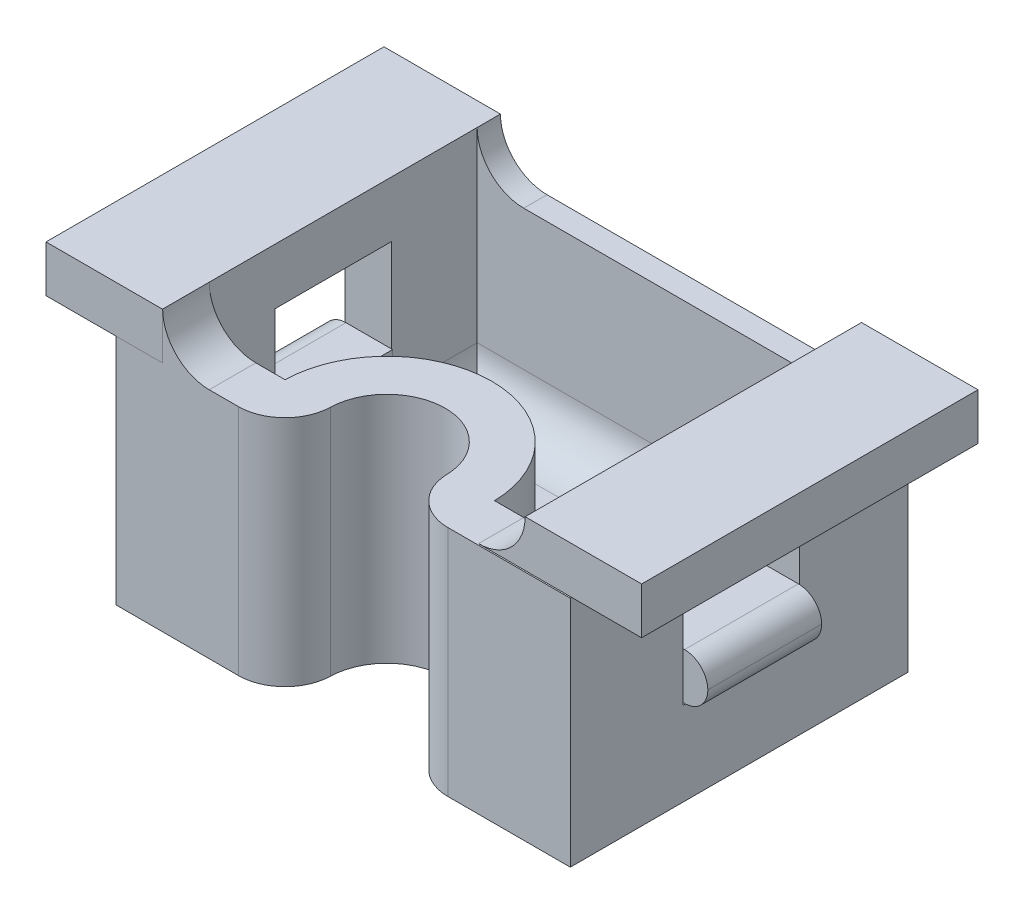
SolidWorks part; units mm, degrees
ref_plane "Front Plane" through (0, 0, 0) normal (0, 0, 1) x (1, 0, 0)
ref_plane "Top Plane" through (0, 0, 0) normal (0, 1, 0) x (1, 0, 0)
ref_plane "Right Plane" through (0, 0, 0) normal (1, 0, 0) x (0, 0, -1)
sketch "Sketch1" plane through (0, 0, 0) normal (0, 1, 0) x (1, 0, 0)
  line L1 (-25.512, 17.5864) -> (-6.012, 17.5864)
  line L2 (-25.512, 17.5864) -> (-25.512, 3.0864)
  line L3 (-25.512, 3.0864) -> (-6.012, 3.0864)
  line L4 (-6.012, 17.5864) -> (-6.012, 3.0864)
  dimension "D1" = 19.5
  dimension "D2" = 14.5
extrude "Boss-Extrude1" add sketch "Sketch1" along normal blind 10
sketch "Sketch2" plane through (0, 10, 0) normal (0, 1, 0) x (1, 0, 0)
  line L0 (-25.512, 3.0864) -> (-6.012, 3.0864) construction
  circle A0 centre (-15.762, 4.9665) radius 2.5
  point P0 (-15.762, 3.0864)
extrude "Cut-Extrude1" cut sketch "Sketch2" against normal blind 10
shell "Shell1" thickness 2 removed face at (-15.762, 10, -8.6497)
fillet "Fillet1" radius 2 2 edges at (-14.1142, 5, -3.0864) (-17.4098, 5, -3.0864)
sketch "Sketch3" plane through (0, 10, 0) normal (0, 1, 0) x (1, 0, 0)
  line L1 (-23.512, 15.5864) -> (-8.012, 15.5864)
  line L2 (-23.512, 15.5864) -> (-23.512, 16.5864)
  line L3 (-23.512, 16.5864) -> (-8.012, 16.5864)
  line L4 (-8.012, 15.5864) -> (-8.012, 16.5864)
  dimension "D1" = 1
extrude "Cut-Extrude3" cut sketch "Sketch3" against normal blind 8
fillet "Fillet2" radius 2 4 edges at (-15.762, 2, -9.4665) (-8.012, 2, -10.8364) (-23.512, 2, -10.8364) (-15.762, 2, -16.5864)
sketch "Sketch4" plane through (0, 10, 0) normal (0, 1, 0) x (1, 0, 0)
  line L0 (-6.012, 17.5864) -> (-25.512, 17.5864) construction
  line L1 (-28.512, 3.0788) -> (-23.512, 3.0788)
  line L2 (-28.512, 3.0788) -> (-28.512, 17.5864)
  line L3 (-28.512, 17.5864) -> (-23.512, 17.5864)
  line L4 (-23.512, 3.0788) -> (-23.512, 17.5864)
  line L6 (-3.012, 3.1463) -> (-8.012, 3.1463)
  line L7 (-3.012, 3.1463) -> (-3.012, 17.5864)
  line L8 (-3.012, 17.5864) -> (-8.012, 17.5864)
  line L9 (-8.012, 3.1463) -> (-8.012, 17.5864)
  dimension "D1" = 5
  dimension "D2" = 5
extrude "Boss-Extrude2" add sketch "Sketch4" along normal blind 2
fillet "Fillet3" radius 2 2 edges at (-8.012, 10, -4.1163)
fillet "Fillet4" radius 2 2 edges at (-8.012, 10, -17.0864)
sketch "Sketch5" plane through (-25.512, 0, 0) normal (-1, 0, 0) x (0, 0, 1)
  line L1 (-12.9156, 3.5992) -> (-7.9156, 3.5992)
  line L2 (-12.9156, 3.5992) -> (-12.9156, 9.5992)
  line L3 (-12.9156, 9.5992) -> (-7.9156, 9.5992)
  line L4 (-7.9156, 3.5992) -> (-7.9156, 9.5992)
  dimension "D1" = 6
  dimension "D2" = 5
extrude "Cut-Extrude4" cut sketch "Sketch5" against normal blind 22
sketch "Sketch6" plane through (0, 3.5992, 0) normal (0, 1, 0) x (1, 0, 0)
  line L1 (-23.4714, 12.9156) -> (-26.4714, 12.9156)
  line L2 (-23.4714, 12.9156) -> (-23.4714, 8.0292)
  line L3 (-23.4714, 8.0292) -> (-26.4714, 8.0292)
  line L4 (-26.4714, 12.9156) -> (-26.4714, 8.0292)
  line L5 (-8.0526, 12.9156) -> (-5.0526, 12.9156)
  line L6 (-8.0526, 12.9156) -> (-8.0526, 8.0292)
  line L7 (-8.0526, 8.0292) -> (-5.0526, 8.0292)
  line L8 (-5.0526, 12.9156) -> (-5.0526, 8.0292)
  dimension "D1" = 3
  dimension "D2" = 3
extrude "Boss-Extrude3" add sketch "Sketch6" along normal blind 2
fillet "Fillet5" radius 1 4 edges at (-5.0526, 3.5992, -10.4724) (-5.0526, 5.5992, -10.4724) (-26.4714, 3.5992, -10.4724) (-26.4714, 5.5992, -10.4724)
